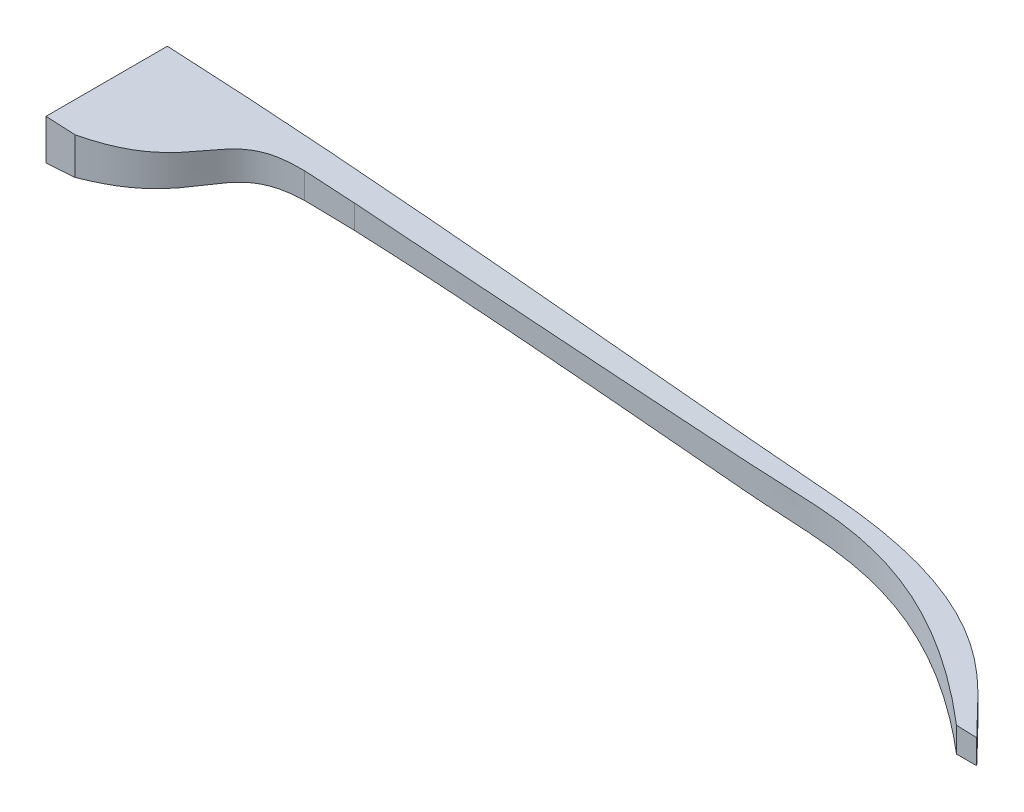
SolidWorks part; units mm, degrees
ref_plane "Front Plane" through (0, 0, 0) normal (0, 0, 1) x (1, 0, 0)
ref_plane "Top Plane" through (0, 0, 0) normal (0, 1, 0) x (1, 0, 0)
ref_plane "Right Plane" through (0, 0, 0) normal (1, 0, 0) x (0, 0, -1)
sketch "Sketch1" plane through (0, 0, 0) normal (0, 1, 0) x (1, 0, 0)
  line L1 (0, 0) -> (146.05, 0)
  line L2 (0, 0) -> (0, 19.05)
  line L3 (0, 19.05) -> (146.05, 19.05)
  line L4 (146.05, 0) -> (146.05, 19.05)
  dimension "D1" = 146.05
  dimension "D2" = 19.05
extrude "Boss-Extrude1" add sketch "Sketch1" along normal blind 15.24
sketch "Sketch3" plane through (0, 0, -19.05) normal (0, 0, -1) x (-1, 0, 0)
  line L0 (0, 15.24) -> (0, 0) construction
  line L1 (-146.05, 15.24) -> (-146.05, 0) construction
  spline S0 degree 3 poles (0, 8.89) (-49.1877, 12.9423) (-97.0981, -0.8062) (-146.05, 0) knots 0 0 0 0 1 1 1 1
  spline S1 degree 3 poles (0, 15.24) (-48.8051, 12.9632) (-97.2173, 5.554) (-146.05, 3.81) knots 0 0 0 0 1 1 1 1
  point P6 (0, 0)
  point P11 (-65.662, 6.5147)
  point P13 (0, 0)
  point P14 (-116.332, 0)
  point P18 (-116.332, 1.0389)
  point P20 (-116.332, 4.445)
  point P21 (-116.332, 4.445)
  point P22 (-116.332, 4.445)
  point P23 (-116.332, 0)
  point P24 (-116.332, 0)
  line M1 (-146.05, 0) -> (0, 0)
  line M2 (0, 0) -> (0, 15.24)
  line M3 (0, 15.24) -> (-146.05, 15.24)
  line M4 (-146.05, 15.24) -> (-146.05, 0)
  dimension "D1" = 6.35
  dimension "D2" = 3.81
  dimension "D3" = 4.445
  dimension "D4" = 3.6908
sketch "Sketch4" plane through (0, 15.24, 0) normal (0, 1, 0) x (1, 0, 0)
  line L0 (146.05, 19.05) -> (0, 19.05) construction
  line L3 (4.5796, 0) -> (142.875, 0)
  line L4 (146.05, 0) -> (146.05, 19.05)
  line L5 (146.05, 19.05) -> (104.3032, 19.05)
  line L6 (0, 0) -> (146.05, 0) construction
  line L7 (146.05, 0) -> (146.05, 19.05) construction
  spline S0 degree 3 poles (4.5796, 0) (17.8286, 4.0431) (13.7936, 14.7107) (45.2643, 14.5853) (87.8612, 15.8591) (105.9828, 16.1084) (121.0936, 18.5899) (142.875, 0) knots 0 0 0 0 0.1669 0.21555 0.456392 0.537847 1 1 1 1
  spline S1 degree 3 poles (104.3032, 19.05) (131.3235, 19.1838) (139.2243, 6.6595) (146.05, 0) knots 0 0 0 0 1 1 1 1
  spline S2 degree 1 poles (26.0327, 14.5352) (69.3777, 15.3249) knots 0 0 1 1
  point P6 (0, 0)
  point P13 (104.3032, 19.05)
  point P17 (0, 0)
  point P18 (0, 0)
  point P19 (93.3832, 14.6006)
  point P20 (25.9759, 16.1188)
  point P21 (0, 0)
  point P22 (93.1594, 15.925)
  line M2 (146.05, 19.05) -> (0, 19.05)
  line M4 (0, 0) -> (146.05, 0)
  dimension "D1" = 3.175
extrude "Cut-Extrude2" cut sketch "Sketch4" against normal blind 19.05 contours S2 S0 M4 | S1 L4 M2 region at (74.3337, 15.24, -7.2282) region at (136.8139, 15.24, -13.5088)
extrude "Cut-Extrude3" cut sketch "Sketch3" against normal through all contours S0 M2 M1 | S1 M3 M4 region at (44.9748, 3.8441, -19.05) region at (99.0693, 11.1958, -19.05)
sketch "Sketch5" plane through (0, 0, 0) normal (-1, 0, 0) x (0, 0, 1)
  line L0 (0, 8.89) -> (-19.05, 8.89) construction
  line L1 (-6.35, 8.89) -> (-12.7, 8.89)
  line L2 (-6.35, 8.89) -> (-6.35, 12.7)
  line L3 (-6.35, 12.7) -> (-12.7, 12.7)
  line L4 (-12.7, 8.89) -> (-12.7, 12.7)
  line L5 (-19.05, 15.24) -> (-19.05, 8.89) construction
  dimension "D1" = 3.81
  dimension "D2" = 6.35
  dimension "D3" = 6.35
extrude "Cut-Extrude4" cut sketch "Sketch5" against normal blind 5.08
